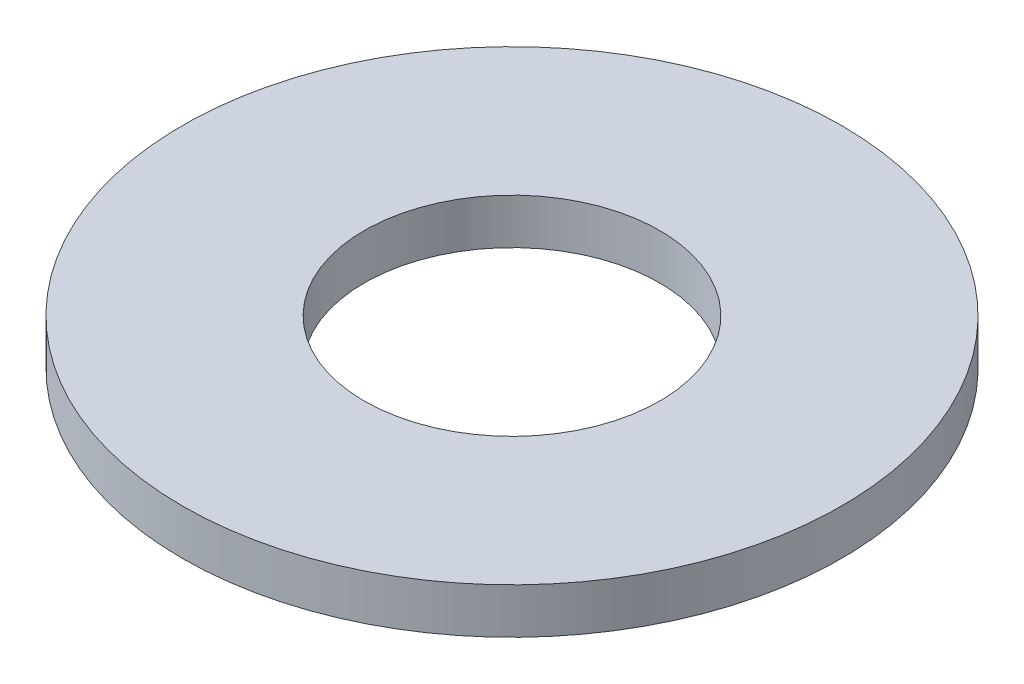
SolidWorks part; units mm, degrees
ref_plane "Front Plane" through (0, 0, 0) normal (0, 0, 1) x (1, 0, 0)
ref_plane "Top Plane" through (0, 0, 0) normal (0, 1, 0) x (1, 0, 0)
ref_plane "Right Plane" through (0, 0, 0) normal (1, 0, 0) x (0, 0, -1)
sketch "Sketch1" plane through (0, 0, 0) normal (0, 1, 0) x (1, 0, 0)
  circle A0 centre (0, 0) radius 72.5
  dimension "FLANGE_OD" = 145
extrude "Boss-Extrude1" add sketch "Sketch1" along normal blind 10
sketch "Sketch2" plane through (0, 0, 0) normal (0, 1, 0) x (1, 0, 0)
  circle A0 centre (0, 0) radius 32.5
  dimension "BORE_D" = 65
extrude "Cut-Extrude1" cut sketch "Sketch2" along normal through all
sketch "Sketch3" plane through (0, 10, 0) normal (0, 1, 0) x (1, 0, 0)
  circle A0 centre (0, 0) radius 21.1138 construction
  circle A1 centre (-21.1138, 0) radius 6.0589
  dimension "BOLT_D" = 12.1177
  dimension "BOLT_PCD" = 42.2276
extrude "Cut-Extrude2" cut sketch "Sketch3" against normal blind 8.5022 rebuild error yes
pattern_circular "CirPattern1" count 3 over 360 rebuild error yes
